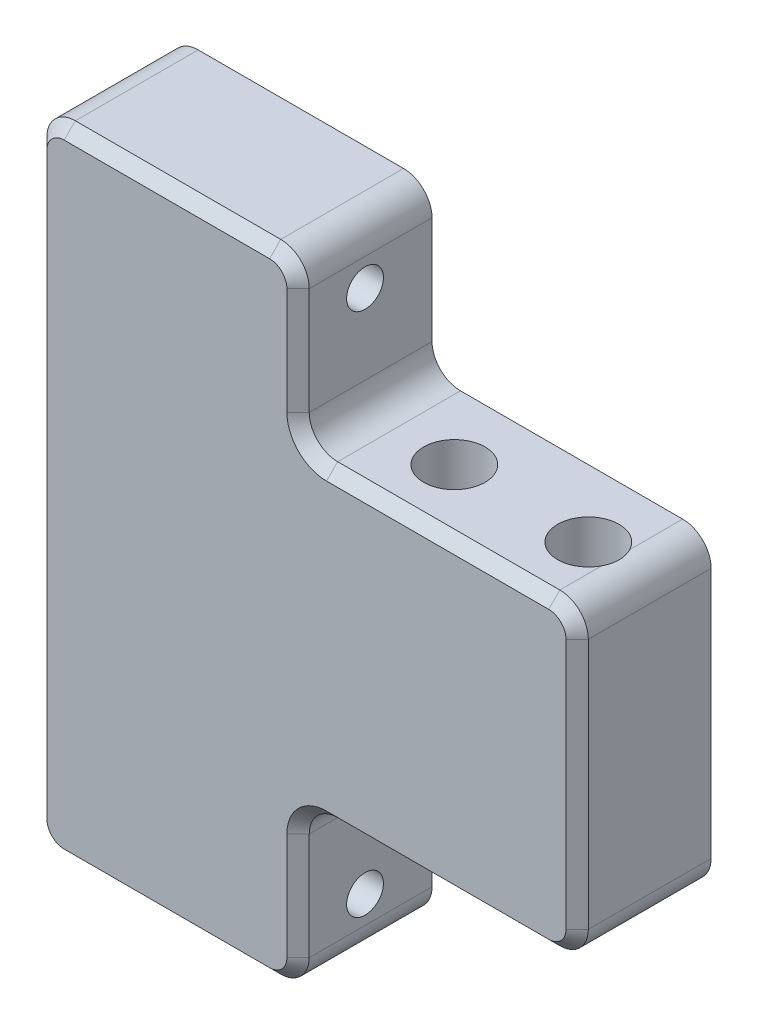
SolidWorks part; units mm, degrees
ref_plane "Front Plane" through (0, 0, 0) normal (0, 0, 1) x (1, 0, 0)
ref_plane "Top Plane" through (0, 0, 0) normal (0, 1, 0) x (1, 0, 0)
ref_plane "Right Plane" through (0, 0, 0) normal (1, 0, 0) x (0, 0, -1)
sketch "Sketch1" plane through (0, 0, 0) normal (0, 0, 1) x (1, 0, 0)
  line L7 (10, 65) -> (10, 8)
  line L9 (33.5, 50.3) -> (33.5, 65)
  line L10 (33.5, 50.3) -> (58.5, 50.3)
  line L11 (10, 8) -> (33.5, 8)
  line L12 (33.5, 8) -> (33.5, 22.7)
  line L13 (10, 65) -> (33.5, 65)
  line L16 (33.5, 22.7) -> (58.5, 22.7)
  line L20 (58.5, 50.3) -> (58.5, 22.7)
extrude "Boss-Extrude1" add sketch "Sketch1" against normal blind 12
sketch "Sketch2" plane through (10, 0, 0) normal (-1, 0, 0) x (0, 0, 1)
  circle A0 centre (-6, 13) radius 1.65
  circle A1 centre (-6, 60) radius 1.65
extrude "Cut-Extrude1" cut sketch "Sketch2" against normal through all
sketch "Sketch3" plane through (0, 22.7, 0) normal (0, -1, 0) x (1, 0, 0)
  circle A0 centre (53.5, -6) radius 5
  circle A1 centre (41.5, -6) radius 5
hole_wizard "M5 Clearance Hole1" positions "Sketch4" profile "Sketch6" hole size "M5" standard "ANSI Metric"
sketch "Sketch4" plane through (0, 22.7, 0) normal (0, -1, 0) x (-1, 0, 0)
  point P0 (-53.5, 6)
  point P3 (-41.5, 6)
sketch "Sketch6" plane through (53.5, 22.7, -6) normal (1, 0, 0) x (0, 0, -1)
  line L0 (0, 0) -> (0, 30)
  line L1 (0, 30) -> (2.75, 28.3476)
  line L2 (2.75, 28.3476) -> (2.75, 0)
  line L5 (2.75, 0) -> (0, 0)
  line L10 (0, 30) -> (-2.75, 28.3476) construction
  line L11 (0, -6.35) -> (0, 107.95) construction
  dimension "Hole Dia." = 5.5
  dimension "Hole Depth" = 30
  dimension "Drill Angle" = 118
fillet "Fillet1" radius 2.55 8 edges at (58.5, 50.3, -6) (33.5, 50.3, -6) (33.5, 65, -6) (10, 65, -6) (10, 8, -6) (33.5, 8, -6) (33.5, 22.7, -6) (58.5, 22.7, -6)
chamfer "Chamfer1" distance 1 angle 45 16 edges at (57.7531, 23.4469, 0) (46, 22.7, 0) (34.2469, 21.9531, 0) (33.5, 15.35, 0) (32.7531, 8.7469, 0) (21.75, 8, 0) (10.7469, 8.7469, 0) (10, 36.5, 0) (10.7469, 64.2531, 0) (21.75, 65, 0) (32.7531, 64.2531, 0) (33.5, 57.65, 0) (34.2469, 51.0469, 0) (46, 50.3, 0) (57.7531, 49.5531, 0) (58.5, 36.5, 0)
